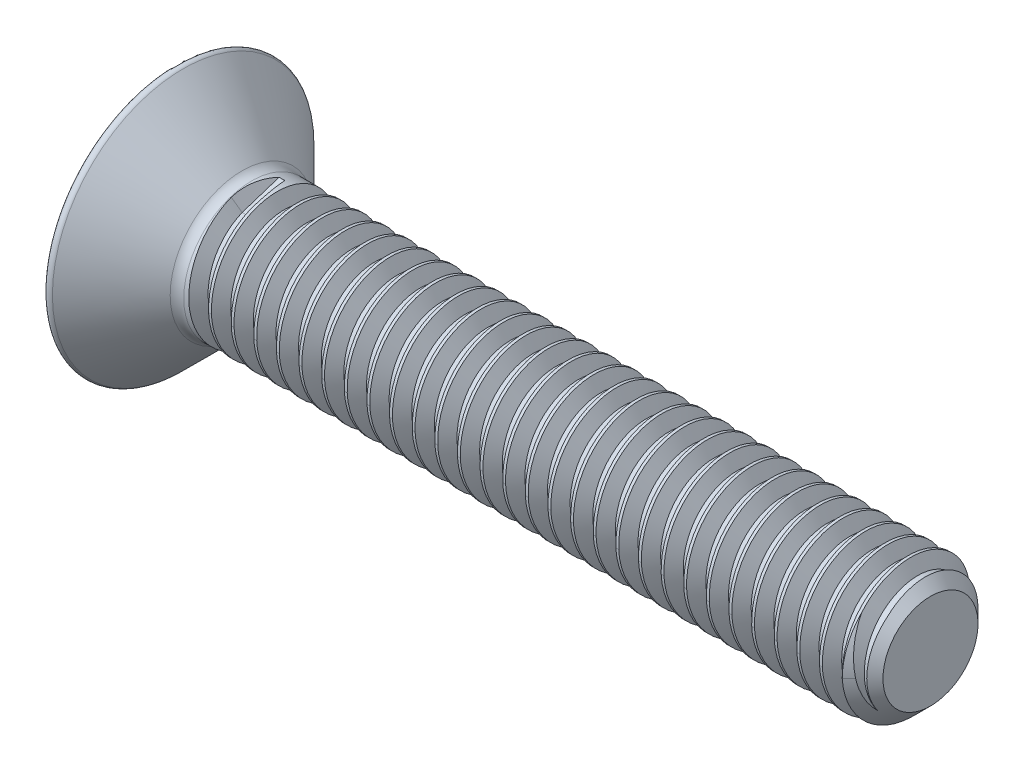
SolidWorks part; units mm, degrees
ref_plane "Front Plane" through (0, 0, 0) normal (0, 0, 1) x (1, 0, 0)
ref_plane "Top Plane" through (0, 0, 0) normal (0, 1, 0) x (1, 0, 0)
ref_plane "Right Plane" through (0, 0, 0) normal (1, 0, 0) x (0, 0, -1)
sketch "Sketch1" plane through (0, 0, 0) normal (0, 0, 1) x (1, 0, 0)
  line L0 (0, 0) -> (30, 0) construction
  line L1 (0, 0) -> (0, 3.06)
  line L2 (0, 3.06) -> (1.4721, 1.5879)
  line L3 (1.56, 0.9604) -> (1.56, 3.3951) construction
  line L4 (1.6843, 1.5) -> (16.6843, 1.5)
  line L5 (16.6843, 1.5) -> (16.6843, 0)
  line L7 (0, 0) -> (16.6843, 0)
  arc A0 (1.4721, 1.5879) -> (1.6843, 1.5) centre (1.6843, 1.8) ccw
  point P11 (1.56, 1.5)
  dimension "D7" = 0.3
  dimension "D1" = 30
  dimension "D2" = 45
  dimension "D3" = 1.56
  dimension "D4" = 3
  dimension "D5" = 1.5
  dimension "D6" = 3.06
  dimension "D8" = 15
revolve "Revolve1" add sketch "Sketch1" angle 360 about L0
chamfer "Chamfer1" distance 0.45 angle 45 1 edges at (16.6843, 0, 1.5)
thread "Thread1" pitch 0.5 profile "Thread Profile1" start angle 0, offset 1, length 0, pitch 0.5, diameter 3
ref_plane "Plane1" through (17.2343, 0, 1.5) normal (0, -1, 0) x (0, 0, 1)
sketch "Thread Profile1" plane through (17.2343, 0, 1.5) normal (0, -1, 0) x (0, 0, 1)
  line L0 (0, 0) -> (0, 0.5) construction
  line L11 (0, 0) -> (0, 0.4375)
  line L12 (0, 0.4375) -> (-0.2706, 0.2812)
  line L13 (-0.2706, 0.2812) -> (-0.2706, 0.1562)
  line L15 (-0.2706, 0.1562) -> (0, 0)
  line L17 (-0.2706, 0.2187) -> (0, 0.2187) construction
  point P2 (0, 0)
  dimension "Pitch" = 0.5
  dimension "Profile_Angle" = 60
  dimension "Profile_Land" = 0.125
  dimension "Profile_Height" = 0.2706
sketch "Sketch5" plane through (0, -0.0001, 0.0002) normal (0.0002, -0.3091, 0.951) x (1, 0, -0.0002)
  line L4 (1.9787, 1.2295) -> (2.1349, 1.5001)
  line L5 (2.1349, 1.5001) -> (1.6974, 1.5001)
  line L6 (1.6974, 1.5001) -> (1.8537, 1.2295)
  line L7 (1.8537, 1.2295) -> (1.9787, 1.2295)
  line L8 (1.9787, 1.2295) -> (2.1349, 1.5001)
  line L9 (2.1349, 1.5001) -> (1.6974, 1.5001)
  line L10 (1.6974, 1.5001) -> (1.8537, 1.2295)
  line L11 (1.8537, 1.2295) -> (1.9787, 1.2295)
  dimension "D1" = 0
extrude "Cut-Extrude2" cut sketch "Sketch5" against normal blind 10
sketch "Sketch6" plane through (0, 0, 0) normal (-1, 0, 0) x (0, 0, 1)
  line L1 (0, 1.1836) -> (-1.025, 0.5918)
  line L2 (-1.025, 0.5918) -> (-1.025, -0.5918)
  line L3 (-1.025, -0.5918) -> (0, -1.1836)
  line L4 (0, -1.1836) -> (1.025, -0.5918)
  line L5 (1.025, -0.5918) -> (1.025, 0.5918)
  line L6 (1.025, 0.5918) -> (0, 1.1836)
  circle A0 centre (0, 0) radius 1.025 construction
  dimension "D1" = 2.05
extrude "Cut-Extrude3" cut sketch "Sketch6" against normal blind 1 draft 2
fillet "Fillet1" radius 0.1 1 edges at (0, 0, 3.06)
fillet "Fillet2" radius 0.1 6 edges at (0, 0, -1.025) (0, -0.8877, -0.5125) (0, -0.8877, 0.5125) (0, 0, 1.025) (0, 0.8877, 0.5125) (0, 0.8877, -0.5125)
